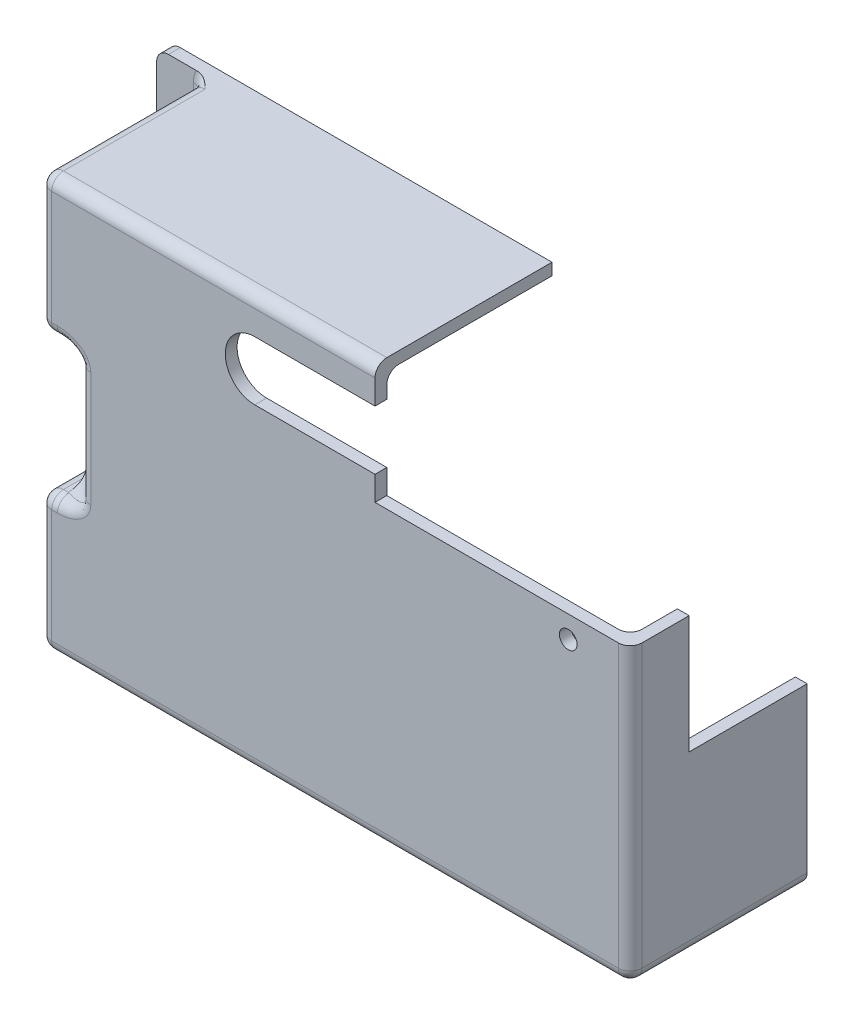
SolidWorks part; units mm, degrees
material "3D_printed_PLA"
ref_plane "Front Plane" through (0, 0, 0) normal (0, 0, 1) x (1, 0, 0)
ref_plane "Top Plane" through (0, 0, 0) normal (0, 1, 0) x (1, 0, 0)
ref_plane "Right Plane" through (0, 0, 0) normal (1, 0, 0) x (0, 0, -1)
sketch "Sketch1" plane through (0, 0, 0) normal (0, 0, 1) x (1, 0, 0)
  line L0 (-44.625, 35) -> (-44.625, -35)
  line L1 (-44.625, -35) -> (63.625, -35)
  line L3 (-44.625, 35) -> (63.625, 35)
  line L4 (63.625, -35) -> (63.625, 35)
  line L5 (-63.625, -35) -> (63.625, 35) construction
  line L6 (-63.625, 35) -> (63.625, -35) construction
  line L7 (-63.625, 35) -> (63.625, 35) construction
  line L9 (-63.625, 35) -> (-63.625, -35) construction
  line L10 (-63.625, -35) -> (63.625, -35) construction
  point P0 (0, 0)
  dimension "D1" = 127.25
  dimension "D2" = 70
  dimension "D3" = 19
extrude "Boss-Extrude1" add sketch "Sketch1" along normal blind 2
sketch "Sketch2" plane through (0, 0, 0) normal (0, 0, -1) x (-1, 0, 0)
  line L0 (-61.625, 33) -> (-61.625, -33)
  line L1 (-61.625, -33) -> (42.625, -33)
  line L2 (42.625, -33) -> (42.625, 33)
  line L3 (42.625, 33) -> (-61.625, 33)
  line L4 (-63.625, 35) -> (-63.625, -35)
  line L5 (-63.625, -35) -> (44.625, -35)
  line L6 (44.625, -35) -> (44.625, 35)
  line L7 (44.625, 35) -> (-63.625, 35)
  line L8 (-63.625, 35) -> (-63.625, -35)
  line L9 (-63.625, -35) -> (44.625, -35)
  line L11 (44.625, 35) -> (-63.625, 35)
  line L16 (44.625, -35) -> (44.625, 35) construction
  line L17 (44.625, -35) -> (44.625, 35)
  dimension "D1" = 0
  dimension "D2" = 2
extrude "Boss-Extrude2" add sketch "Sketch2" along normal blind 28
sketch "Sketch5" plane through (0, 0, 2) normal (0, 0, 1) x (1, 0, 0)
  line L0 (-44.625, 11.75) -> (-26.625, 11.75)
  line L2 (-26.625, 11.75) -> (-26.625, 14.25)
  line L3 (-26.625, 14.25) -> (-35.625, 14.25)
  line L4 (-35.625, 14.25) -> (-35.625, 35)
  line L5 (63.625, 35) -> (-44.625, 35) construction
  line L6 (-35.625, 35) -> (-44.625, 35)
  line L7 (-44.625, 35) -> (-44.625, 11.75)
  line L8 (-42.625, 0) -> (-39.8001, 0) construction
  line L9 (-42.625, -33) -> (-42.625, 33) construction
  line L10 (-35.625, -35) -> (-44.625, -35)
  line L11 (-35.625, -14.25) -> (-35.625, -35)
  line L12 (-26.625, -14.25) -> (-35.625, -14.25)
  line L13 (-26.625, -11.75) -> (-26.625, -14.25)
  line L14 (-44.625, -11.75) -> (-26.625, -11.75)
  line L15 (-44.625, -35) -> (-44.625, -11.75)
  line L16 (-44.625, 35) -> (-44.625, -35) construction
  point P2 (0, 0)
  point P22 (0, 0)
  point P24 (0, 0)
  point P25 (0, 0)
  dimension "D1" = 23.5
  dimension "D2" = 18
  dimension "D3" = 2.5
  dimension "D4" = 9
extrude "Boss-Extrude3" add sketch "Sketch5" against normal offset from surface (29.75 mm away) 0.25 up to face at (9.5, 0, -28)
sketch "Sketch6" plane through (0, 0, 2) normal (0, 0, 1) x (1, 0, 0)
  line L0 (-42.625, -11.75) -> (-26.625, -11.75) construction
  line L1 (-26.625, 11.75) -> (-33.625, 11.75)
  line L2 (-26.625, 11.75) -> (-26.625, -11.75)
  line L3 (-26.625, -11.75) -> (-33.625, -11.75)
  line L4 (-33.625, 11.75) -> (-33.625, -11.75)
  dimension "D1" = 7
extrude "Boss-Extrude4" add sketch "Sketch6" against normal blind 5.75
sketch "Sketch7" plane through (-44.625, 0, 0) normal (-1, 0, 0) x (0, 0, 1)
  line L1 (2, -11.75) -> (-28, -11.75)
  line L2 (2, -11.75) -> (2, 11.75)
  line L3 (2, 11.75) -> (-28, 11.75)
  line L4 (-28, -11.75) -> (-28, 11.75)
  line L5 (-28, -35) -> (-28, 35) construction
  line L6 (-28, 11.75) -> (2, -11.75) construction
  line L7 (-28, -11.75) -> (2, 11.75) construction
  line L9 (2, 35) -> (2, -35) construction
  point P4 (-13, 0)
  dimension "D1" = 23.5
extrude "Cut-Extrude2" cut sketch "Sketch7" against normal up to vertex
sketch "Sketch8" plane through (0, -35, 0) normal (0, -1, 0) x (1, 0, 0)
  line L0 (63.625, -28) -> (-44.625, -28) construction
  line L1 (-44.625, 2) -> (-36.425, 2)
  line L2 (-44.625, 2) -> (-44.625, -26)
  line L3 (-44.625, -26) -> (-36.425, -26)
  line L4 (-36.425, 2) -> (-36.425, -26)
  line L5 (-35.625, 0) -> (-35.625, -27.75) construction
  point P4 (0, 0)
  point P9 (0, 0)
  point P10 (0, 0)
  dimension "D1" = 2
  dimension "D2" = 0.8
extrude "Cut-Extrude3" cut sketch "Sketch8" against normal through all both and the other way through all
chamfer "Chamfer1" distance 5 angle 45 1 edges at (-33.625, 0, 2)
fillet "Fillet1" radius 2 32 edges at (13, -33, 0) (61.625, 0, 0) (13, 33, 0) (13.6, -35, 2) (13.6, 35, 2) (63.625, 0, 2) (-42.625, 33, -27.875) (-42.625, -33, -27.875) (61.625, -33, -14) (61.625, 33, -14) (63.625, 35, -13) (63.625, -35, -13) (-35.625, -23.625, 0) (-35.625, 23.625, 0) (-31.125, 14.25, 0) (-26.625, 0, 0) (-31.125, -14.25, 0) (-36.425, 23.375, 2) (-36.425, -23.375, 2) (-32.525, -11.75, 2) (-28.625, 0, 2) (-32.525, 11.75, 2) (-36.425, 11.75, -12) (-36.425, -11.75, -12) (-31.125, -11.75, -0.5) (-31.125, 11.75, -0.5) (-36.425, -35, -12) (-36.425, 35, -12) (-44.625, 35, -27) (-44.625, 11.75, -27) (-44.625, -11.75, -27) (-44.625, -35, -27)
sketch "Sketch3" plane through (0, 0, 2) normal (0, 0, 1) x (1, 0, 0)
  line L0 (63.625, 33) -> (63.625, -33) construction
  line L1 (63.625, 14.75) -> (20.375, 14.75)
  line L2 (63.625, 14.75) -> (63.625, 35)
  line L3 (63.625, 35) -> (20.375, 35)
  line L4 (20.375, 14.75) -> (20.375, 35)
  line L5 (-34.425, 35) -> (61.625, 35) construction
  dimension "D1" = 43.25
  dimension "D2" = 20.25
extrude "Cut-Extrude1" cut sketch "Sketch3" against normal through all both and the other way through all
fillet "Fillet2" radius 2 6 edges at (-35.8392, -12.3358, -26) (-35.8392, -34.4142, -26) (-35.8392, 34.4142, -26) (-35.8392, 12.3358, -26) (-36.425, -23.375, -26) (-36.425, 23.375, -26)
sketch "Sketch9" plane through (0, 0, -26) normal (0, 0, 1) x (1, 0, 0)
  line L0 (63.625, 14.75) -> (63.625, -33) construction
  circle A0 centre (-41.875, -18.75) radius 1.5
  circle A1 centre (-41.875, 18.75) radius 1.5
  point P4 (-25.1924, -27.125)
  dimension "D1" = 3
  dimension "D2" = 105.5
  dimension "D3" = 37.5
  dimension "D4" = 18.75
extrude "Cut-Extrude4" cut sketch "Sketch9" along normal through all and the other way blind 2.5
sketch "Sketch10" plane through (0, 0, -26) normal (0, 0, 1) x (1, 0, 0)
  line L3 (-38.425, -33) -> (-38.425, -13.75) construction
  circle A0 centre (-38.425, 18.75) radius 1.5
  circle A1 centre (-38.425, -18.75) radius 1.5
  point P2 (-38.425, 27.125)
  point P7 (0, 0)
  point P8 (0, 0)
  point P9 (0, 0)
  point P10 (0, 0)
  point P11 (0, 0)
  point P14 (0, 0)
  point P15 (0, 0)
  dimension "D1" = 3
  dimension "D2" = 37.5
  dimension "D3" = 18.75
extrude "Cut-Extrude5" cut sketch "Sketch10" along normal through all
sketch "Sketch11" plane through (0, 0, 2) normal (0, 0, 1) x (1, 0, 0)
  line L0 (61.625, 14.75) -> (20.375, 14.75) construction
  line L1 (63.625, 14.75) -> (63.625, -33) construction
  circle A1 centre (53.125, 11) radius 1.5
  point P3 (0, 0)
  dimension "D1" = 3.75
  dimension "D2" = 10.5
extrude "Cut-Extrude6" cut sketch "Sketch11" against normal through all both and the other way through all
sketch "Sketch12" plane through (0, 0, 2) normal (0, 0, 1) x (1, 0, 0)
  line L0 (20.375, 23.875) -> (0, 23.875) construction
  line L1 (20.375, 14.75) -> (20.375, 33) construction
  line L2 (20.375, 18.875) -> (0, 18.875)
  line L3 (20.375, 28.875) -> (0, 28.875)
  arc A0 (20.375, 18.875) -> (20.375, 28.875) centre (20.375, 23.875) ccw
  arc A1 (0, 28.875) -> (0, 18.875) centre (0, 23.875) ccw
  point P4 (10.1875, 23.875)
  dimension "D1" = 5
extrude "Cut-Extrude7" cut sketch "Sketch12" against normal through all both and the other way through all
sketch "Sketch13" plane through (63.625, 0, 0) normal (1, 0, 0) x (0, 0, -1)
  line L0 (28, 14.75) -> (28, -33) construction
  line L1 (28, 14.75) -> (8, 14.75)
  line L2 (28, 14.75) -> (28, -5.25)
  line L3 (28, -5.25) -> (8, -5.25)
  line L4 (8, 14.75) -> (8, -5.25)
  line L5 (28, 14.75) -> (0, 14.75) construction
  line L6 (-2, -33) -> (-2, 14.75) construction
  dimension "D1" = 10
  dimension "D2" = 20
extrude "Cut-Extrude8" cut sketch "Sketch13" against normal blind 10
